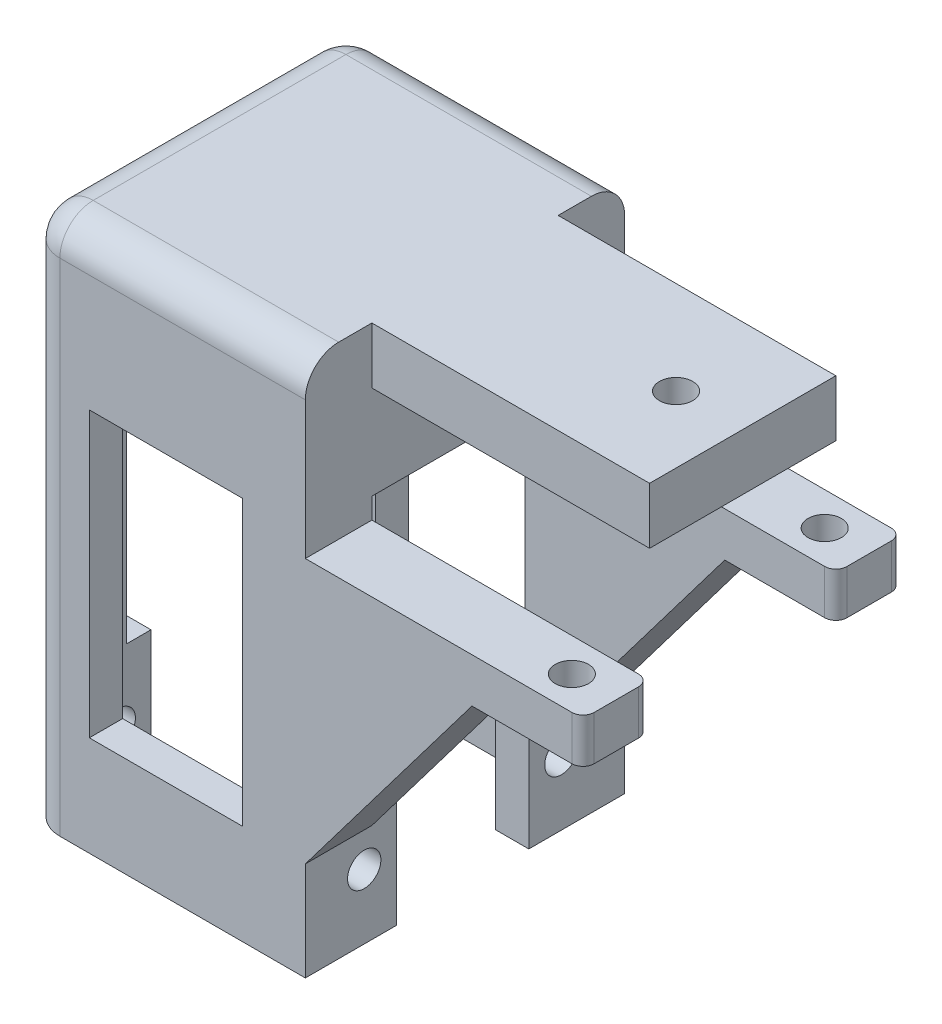
SolidWorks part; units mm, degrees
ref_plane "Front Plane" through (0, 0, 0) normal (0, 0, 1) x (1, 0, 0)
ref_plane "Top Plane" through (0, 0, 0) normal (0, 1, 0) x (1, 0, 0)
ref_plane "Right Plane" through (0, 0, 0) normal (1, 0, 0) x (0, 0, -1)
sketch "Sketch4" plane through (0, 0, 0) normal (0, 1, 0) x (1, 0, 0)
  line L1 (-12.55, 14.375) -> (12.55, 14.375)
  line L2 (-12.55, 14.375) -> (-12.55, -14.375)
  line L3 (-12.55, -14.375) -> (12.55, -14.375)
  line L4 (12.55, 14.375) -> (12.55, -14.375)
  line L5 (-12.55, 14.375) -> (12.55, -14.375) construction
  line L6 (-12.55, -14.375) -> (12.55, 14.375) construction
  point P0 (0, 0)
  dimension "D1" = 28.75
  dimension "D2" = 25.1
extrude "Boss-Extrude2" add sketch "Sketch4" along normal blind 53
sketch "Sketch5" plane through (0, 0, 0) normal (0, -1, 0) x (-1, 0, 0)
  line L0 (-12.55, -14.375) -> (-12.55, 14.375) construction
  line L1 (9.55, -11.375) -> (-9.55, -11.375)
  line L2 (9.55, -11.375) -> (9.55, 11.375)
  line L3 (9.55, 11.375) -> (-9.55, 11.375)
  line L4 (-9.55, -11.375) -> (-9.55, 11.375)
  line L5 (9.55, -11.375) -> (-9.55, 11.375) construction
  line L6 (9.55, 11.375) -> (-9.55, -11.375) construction
  line L7 (-12.55, 14.375) -> (12.55, 14.375) construction
  point P0 (0, 0)
  dimension "D1" = 22.75
  dimension "D2" = 19.1
  dimension "D3" = 3
  dimension "D4" = 3
extrude "Cut-Extrude1" cut sketch "Sketch5" against normal blind 21.67
fillet "Fillet1" radius 4.1 2 edges at (0, 21.67, -11.375) (0, 21.67, 11.375)
sketch "Sketch6" plane through (0, 21.67, 0) normal (0, -1, 0) x (-1, 0, 0)
  line L1 (2.5, 4) -> (-2.5, 4)
  line L2 (2.5, 4) -> (2.5, -4)
  line L3 (2.5, -4) -> (-2.5, -4)
  line L4 (-2.5, 4) -> (-2.5, -4)
  line L5 (2.5, 4) -> (-2.5, -4) construction
  line L6 (2.5, -4) -> (-2.5, 4) construction
  point P0 (0, 0)
  dimension "D1" = 5
  dimension "D2" = 8
extrude "Cut-Extrude2" cut sketch "Sketch6" against normal blind 4.67
sketch "Sketch7" plane through (12.55, 0, 0) normal (1, 0, 0) x (0, 0, -1)
  line L0 (-14.375, 53) -> (-14.375, 0) construction
  line L1 (-8.3848, -17.57) -> (8.3848, -17.57)
  line L2 (-8.3848, -17.57) -> (-8.3848, 17.57)
  line L3 (-8.3848, 17.57) -> (8.3848, 17.57)
  line L4 (8.3848, -17.57) -> (8.3848, 17.57)
  line L5 (-8.3848, -17.57) -> (8.3848, 17.57) construction
  line L6 (-8.3848, 17.57) -> (8.3848, -17.57) construction
  point P0 (0, 0)
  dimension "D1" = 35.14
  dimension "D2" = 5.9902
extrude "Cut-Extrude3" cut sketch "Sketch7" against normal blind 40
sketch "Sketch8" plane through (0, 0, -14.375) normal (0, 0, -1) x (-1, 0, 0)
  line L0 (12.55, 53) -> (12.55, 0) construction
  line L1 (-6.8992, -17.57) -> (6.8992, -17.57)
  line L2 (-6.8992, -17.57) -> (-6.8992, 17.57)
  line L3 (-6.8992, 17.57) -> (6.8992, 17.57)
  line L4 (6.8992, -17.57) -> (6.8992, 17.57)
  line L5 (-6.8992, -17.57) -> (6.8992, 17.57) construction
  line L6 (-6.8992, 17.57) -> (6.8992, -17.57) construction
  line L7 (-12.55, 53) -> (-12.55, 0) construction
  point P0 (0, 0)
  dimension "D1" = 35.14
  dimension "D2" = 5.6508
  dimension "D3" = 5.6508
extrude "Cut-Extrude4" cut sketch "Sketch8" against normal blind 40
sketch "Sketch9" plane through (0, 0, 0) normal (0, -1, 0) x (1, 0, 0)
  line L0 (-9.55, 8.3848) -> (-12.55, 8.3848)
  line L1 (-12.55, 8.3848) -> (-12.55, 14.375)
  line L2 (-12.55, 14.375) -> (-6.8992, 14.375)
  line L3 (-6.8992, 14.375) -> (-6.8992, 11.375)
  line L4 (-6.8992, 11.375) -> (-9.55, 11.375)
  line L5 (-9.55, 11.375) -> (-9.55, 8.3848)
  line L6 (-9.55, -8.3848) -> (-12.55, -8.3848)
  line L7 (-12.55, -8.3848) -> (-12.55, -14.375)
  line L8 (-12.55, -14.375) -> (-6.8992, -14.375)
  line L9 (-6.8992, -14.375) -> (-6.8992, -11.375)
  line L10 (-6.8992, -11.375) -> (-9.55, -11.375)
  line L11 (-9.55, -11.375) -> (-9.55, -8.3848)
  line L12 (6.8992, -11.375) -> (6.8992, -14.375)
  line L13 (6.8992, -14.375) -> (12.55, -14.375)
  line L14 (12.55, -14.375) -> (12.55, -8.3848)
  line L15 (12.55, -8.3848) -> (9.55, -8.3848)
  line L16 (9.55, -8.3848) -> (9.55, -11.375)
  line L17 (9.55, -11.375) -> (6.8992, -11.375)
  line L18 (9.55, 8.3848) -> (12.55, 8.3848)
  line L19 (12.55, 8.3848) -> (12.55, 14.375)
  line L20 (12.55, 14.375) -> (6.8992, 14.375)
  line L21 (6.8992, 14.375) -> (6.8992, 11.375)
  line L22 (6.8992, 11.375) -> (9.55, 11.375)
  line L23 (9.55, 11.375) -> (9.55, 8.3848)
extrude "Boss-Extrude3" add sketch "Sketch9" along normal blind 17
sketch "Sketch10" plane through (-6.8992, 0, 0) normal (1, 0, 0) x (0, 0, -1)
  line L0 (-11.375, 17.57) -> (-11.375, -17) construction
  line L1 (-14.375, -17) -> (-11.375, -17)
  line L2 (-14.375, -17) -> (-14.375, -8)
  line L3 (-14.375, -8) -> (-11.375, -8)
  line L4 (-11.375, -17) -> (-11.375, -8)
  dimension "D1" = 9
extrude "Boss-Extrude4" add sketch "Sketch10" along normal blind 13.8
sketch "Sketch11" plane through (6.8992, 0, 0) normal (-1, 0, 0) x (0, 0, 1)
  line L0 (-11.375, 17.57) -> (-11.375, -17) construction
  line L1 (-14.375, -17) -> (-11.375, -17)
  line L2 (-14.375, -17) -> (-14.375, -8)
  line L3 (-14.375, -8) -> (-11.375, -8)
  line L4 (-11.375, -17) -> (-11.375, -8)
  dimension "D1" = 9
extrude "Boss-Extrude5" add sketch "Sketch11" along normal blind 13.8
sketch "Sketch12" plane through (0, 0, -8.3848) normal (0, 0, 1) x (1, 0, 0)
  line L0 (-9.55, 17.57) -> (-9.55, -17) construction
  line L1 (-12.55, -17) -> (-9.55, -17)
  line L2 (-12.55, -17) -> (-12.55, -5)
  line L3 (-12.55, -5) -> (-9.55, -5)
  line L4 (-9.55, -17) -> (-9.55, -5)
  line L5 (12.55, -17) -> (12.55, 17.57) construction
  line L6 (9.55, -17) -> (12.55, -17)
  line L7 (9.55, -17) -> (9.55, -5)
  line L8 (9.55, -5) -> (12.55, -5)
  line L9 (12.55, -17) -> (12.55, -5)
  dimension "D1" = 12
  dimension "D2" = 12
extrude "Boss-Extrude6" add sketch "Sketch12" along normal blind 16.77
sketch "Sketch24" plane through (12.55, 0, 0) normal (1, 0, 0) x (0, 0, -1)
  line L1 (-8.3848, -5) -> (8.3848, -5) construction
  circle A0 centre (8.675, -11.18) radius 1.5
  circle A1 centre (-9.075, -11.18) radius 1.5
  dimension "D3" = 3
  dimension "D5" = 3
  dimension "D1" = 17.75
  dimension "D2" = 6.18
  dimension "D6" = 6.18
extrude "Cut-Extrude6" cut sketch "Sketch24" against normal blind 40.8
sketch "Sketch25" plane through (-12.55, 0, 0) normal (-1, 0, 0) x (0, 0, 1)
  line L0 (14.375, 53) -> (14.375, -17) construction
  line L1 (-14.375, 53) -> (14.375, 53)
  line L2 (-14.375, 53) -> (-14.375, 31.0749)
  line L3 (-14.375, 31.0749) -> (14.375, 31.0749)
  line L4 (14.375, 53) -> (14.375, 31.0749)
extrude "Cut-Extrude7" cut sketch "Sketch25" against normal blind 40.8
sketch "Sketch26" plane through (-12.55, 0, 0) normal (-1, 0, 0) x (0, 0, 1)
  line L0 (8.3848, -5) -> (-8.3848, -5) construction
  line L1 (-5.7417, -5) -> (6.1723, -5)
  line L2 (-5.7417, -5) -> (-5.7417, -17)
  line L3 (-5.7417, -17) -> (6.1723, -17)
  line L4 (6.1723, -5) -> (6.1723, -17)
  line L5 (14.375, -17) -> (-14.375, -17) construction
extrude "Cut-Extrude8" cut sketch "Sketch26" against normal blind 40.8
sketch "Sketch30" plane through (12.55, 0, 0) normal (1, 0, 0) x (0, 0, -1)
  line L0 (14.375, 31.0749) -> (14.375, -17) construction
  line L5 (-14.375, 31.0749) -> (14.375, 31.0749)
  line L6 (-14.375, 31.0749) -> (-14.375, 26.0049)
  line L7 (-14.375, 26.0049) -> (14.375, 26.0049)
  line L8 (14.375, 31.0749) -> (14.375, 26.0049)
  dimension "D1" = 5.07
extrude "Boss-Extrude10" add sketch "Sketch30" along normal blind 30
sketch "Sketch32" plane through (12.55, 0, 0) normal (1, 0, 0) x (0, 0, -1)
  line L0 (-14.375, 26.0049) -> (-14.375, -17) construction
  line L1 (-14.375, 15.7049) -> (-8.3848, 15.7049)
  line L2 (-14.375, 15.7049) -> (-14.375, -8.1053)
  line L3 (-14.375, -8.1053) -> (-8.3848, -8.1053)
  line L4 (-8.3848, 15.7049) -> (-8.3848, -8.1053)
  line L5 (-14.375, 26.0049) -> (14.375, 26.0049) construction
  line L6 (8.3848, -5) -> (8.3848, 17.57) construction
  line L7 (8.3848, 15.7049) -> (14.375, 15.7049)
  line L8 (8.3848, 15.7049) -> (8.3848, -8.1053)
  line L9 (8.3848, -8.1053) -> (14.375, -8.1053)
  line L10 (14.375, 15.7049) -> (14.375, -8.1053)
  line L11 (14.375, 26.0049) -> (14.375, -17) construction
  point P16 (0, 0)
  dimension "D1" = 10.3
extrude "Boss-Extrude13" add sketch "Sketch32" along normal blind 30
sketch "Sketch35" plane through (0, 0, -14.375) normal (0, 0, -1) x (-1, 0, 0)
  line L0 (-42.55, 11.7049) -> (-27.55, 11.7049)
  line L1 (-42.55, -8.1053) -> (-42.55, 15.7049) construction
  line L2 (-27.55, 11.7049) -> (-12.55, -8.1053)
  line L3 (-12.55, -8.1053) -> (-42.55, -8.1053)
  line L4 (-42.55, -8.1053) -> (-42.55, 11.7049)
  line L5 (-42.55, 15.7049) -> (-12.55, 15.7049) construction
  dimension "D1" = 15
  dimension "D2" = 4
extrude "Cut-Extrude9" cut sketch "Sketch35" against normal blind 30 contours L0 L2 L3 L4
sketch "Sketch36" plane through (0, 31.0749, 0) normal (0, 1, 0) x (1, 0, 0)
  line L0 (42.55, -14.375) -> (-12.55, -14.375) construction
  line L1 (42.55, 14.375) -> (37.55, 14.375)
  line L2 (42.55, 14.375) -> (42.55, -14.375)
  line L3 (42.55, -14.375) -> (37.55, -14.375)
  line L4 (37.55, 14.375) -> (37.55, -14.375)
  dimension "D1" = 5
extrude "Cut-Extrude10" cut sketch "Sketch36" against normal blind 30 contours L4 L3 L2 L1
sketch "Sketch38" plane through (37.55, 0, 0) normal (1, 0, 0) x (0, 0, -1)
  line L0 (14.375, 26.0049) -> (-14.375, 26.0049) construction
  line L1 (-14.375, 31.0749) -> (-8.385, 31.0749)
  line L2 (-14.375, 31.0749) -> (-14.375, 26.0049)
  line L3 (-14.375, 26.0049) -> (-8.385, 26.0049)
  line L4 (-8.385, 31.0749) -> (-8.385, 26.0049)
  line L6 (14.375, 31.0749) -> (8.385, 31.0749)
  line L7 (14.375, 31.0749) -> (14.375, 26.0049)
  line L8 (14.375, 26.0049) -> (8.385, 26.0049)
  line L9 (8.385, 31.0749) -> (8.385, 26.0049)
  dimension "D1" = 5.99
  dimension "D2" = 5.99
extrude "Cut-Extrude11" cut sketch "Sketch38" against normal blind 25
sketch "Sketch39" plane through (0, 11.7049, 0) normal (0, -1, 0) x (-1, 0, 0)
  line L0 (-37.55, 8.3848) -> (-37.55, 14.375) construction
  line L1 (-37.55, -14.375) -> (-37.55, -8.3848) construction
  circle A0 centre (-33.55, 11.3799) radius 1.5
  circle A1 centre (-33.55, -11.3799) radius 1.5
  dimension "D1" = 3
  dimension "D3" = 3
  dimension "D2" = 4
  dimension "D4" = 4
extrude "Cut-Extrude12" cut sketch "Sketch39" against normal blind 25
sketch "Sketch40" plane through (0, 26.0049, 0) normal (0, -1, 0) x (1, 0, 0)
  line L0 (37.55, -8.385) -> (37.55, 8.385) construction
  circle A0 centre (31.55, 0) radius 1.5
  dimension "D2" = 3
  dimension "D1" = 6
extrude "Cut-Extrude13" cut sketch "Sketch40" against normal blind 25
fillet "Fillet4" radius 3 3 edges at (0, 31.0749, -14.375) (-12.55, 31.0749, 0) (0, 31.0749, 14.375)
fillet "Fillet5" radius 3 4 edges at (-11.6713, 30.1962, 13.4963) (-11.6713, 30.1962, -13.4963) (-12.55, 5.5375, 14.375) (-12.55, 5.5375, -14.375)
fillet "Fillet7" radius 1 4 edges at (37.55, 13.7049, 14.375) (37.55, 13.7049, 8.3848) (37.55, 13.7049, -8.3848) (37.55, 13.7049, -14.375)
